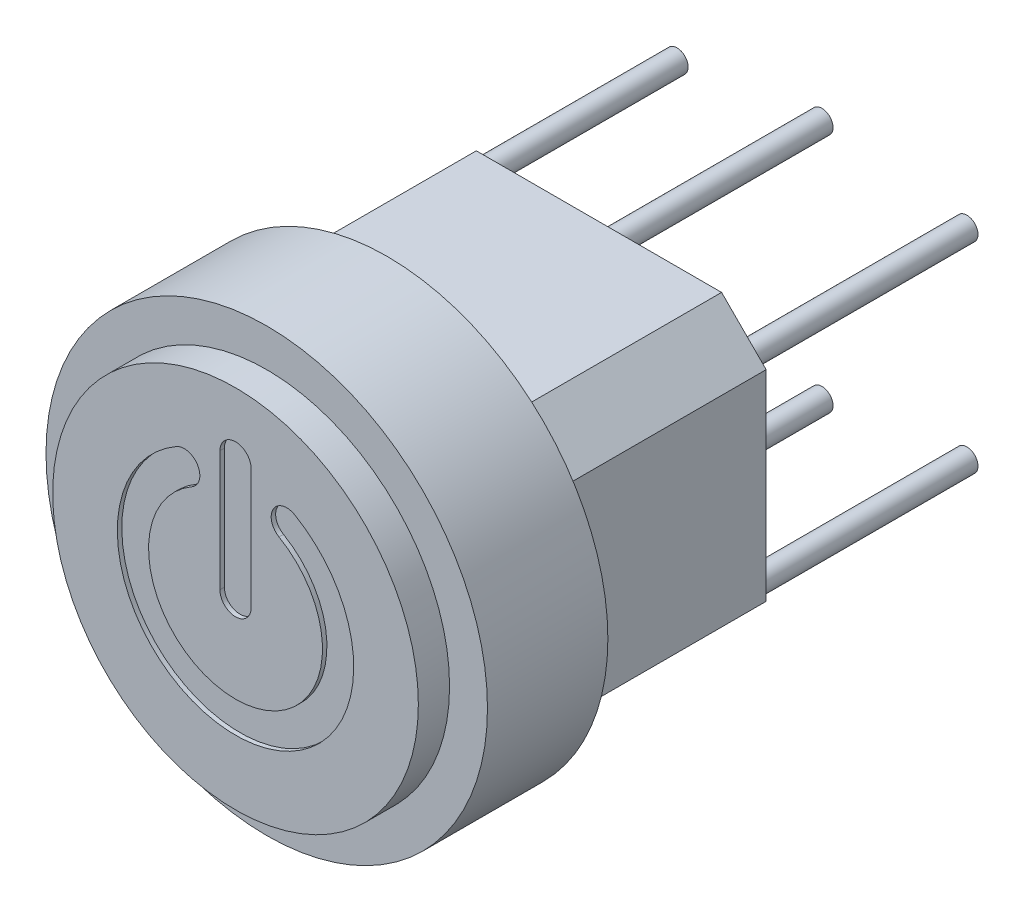
SolidWorks part; units mm, degrees
ref_plane "Plan de face" through (0, 0, 0) normal (0, 0, 1) x (1, 0, 0)
ref_plane "Plan de dessus" through (0, 0, 0) normal (0, 1, 0) x (1, 0, 0)
ref_plane "Plan de droite" through (0, 0, 0) normal (1, 0, 0) x (0, 0, -1)
sketch "Esquisse1" plane through (0, 0, 0) normal (0, 0, 1) x (1, 0, 0)
  circle A0 centre (0, 0) radius 4.95
  dimension "D1" = 9.9
extrude "Boss.-Extru.1" add sketch "Esquisse1" along normal blind 2.7
sketch "Esquisse2" plane through (0, 0, 0) normal (0, 0, -1) x (-1, 0, 0)
  line L1 (-3.75, 3.25) -> (3.75, 3.25)
  line L2 (-3.75, 3.25) -> (-3.75, -3.25)
  line L3 (-3.75, -3.25) -> (3.75, -3.25)
  line L4 (3.75, 3.25) -> (3.75, -3.25)
  line L5 (-3.75, 3.25) -> (3.75, -3.25) construction
  line L6 (-3.75, -3.25) -> (3.75, 3.25) construction
  point P0 (0, 0)
  dimension "D1" = 6.5
  dimension "D2" = 7.5
extrude "Boss.-Extru.2" add sketch "Esquisse2" along normal blind 4.75
sketch "Esquisse3" plane through (0, 0, 2.7) normal (0, 0, 1) x (1, 0, 0)
  circle A0 centre (0, 0) radius 4.1
  dimension "D1" = 8.2
extrude "Boss.-Extru.3" add sketch "Esquisse3" along normal blind 0.7
chamfer "Chanfrein1" distance 1 angle 45 4 edges at (-3.75, 3.25, -2.375) (-3.75, -3.25, -2.375) (3.75, -3.25, -2.375) (3.75, 3.25, -2.375)
sketch "Esquisse4" plane through (0, 0, -4.75) normal (0, 0, -1) x (-1, 0, 0)
  line L0 (0, -3.25) -> (0, 3.25) construction
  line L1 (-2.75, -3.25) -> (2.75, -3.25) construction
  line L2 (2.75, 3.25) -> (-2.75, 3.25) construction
  line L3 (-3.25, 2.25) -> (3.25, 2.25) construction
  line L4 (-3.75, 0) -> (3.75, 0) construction
  line L5 (-3.75, 2.25) -> (-3.75, -2.25) construction
  line L6 (3.75, -2.25) -> (3.75, 2.25) construction
  circle A0 centre (-3.25, 2.25) radius 0.25
  circle A1 centre (0, 2.7) radius 0.25
  circle A2 centre (3.25, 2.25) radius 0.25
  circle A3 centre (3.25, -2.25) radius 0.25
  circle A4 centre (0, -2.7) radius 0.25
  circle A5 centre (-3.25, -2.25) radius 0.25
  point P12 (0, 2.25)
  point P13 (0, 0)
  dimension "D2" = 0.5
  dimension "D3" = 0.5
  dimension "D4" = 0.5
  dimension "D1" = 6.5
  dimension "D5" = 2.25
  dimension "D6" = 2.7
extrude "Boss.-Extru.4" add sketch "Esquisse4" along normal blind 5
sketch "Esquisse5" plane through (0, 0, 3.4) normal (0, 0, 1) x (1, 0, 0)
  line L0 (1.325, 2.295) -> (0.975, 1.6887) construction
  line L1 (-1.325, 2.295) -> (-0.975, 1.6887) construction
  line L2 (0.975, 1.6887) -> (0, 0) construction
  line L3 (0, 0) -> (-0.975, 1.6887) construction
  line L4 (0, 0) -> (0, 2.7) construction
  line L5 (0, 2.7) -> (0, 0) construction
  line L6 (0.35, 2.7) -> (0.35, 0)
  line L7 (-0.35, 2.7) -> (-0.35, 0)
  arc A0 (-0.975, 1.6887) -> (0.975, 1.6887) centre (0, 0) ccw
  arc A1 (-1.325, 2.295) -> (1.325, 2.295) centre (0, 0) ccw
  arc A2 (-1.325, 2.295) -> (-0.975, 1.6887) centre (-1.15, 1.9919) cw
  arc A3 (1.325, 2.295) -> (0.975, 1.6887) centre (1.15, 1.9919) ccw
  arc A4 (0.35, 2.7) -> (-0.35, 2.7) centre (0, 2.7) ccw
  arc A5 (-0.35, 0) -> (0.35, 0) centre (0, 0) ccw
  point P11 (0, 1.35)
  dimension "D5" = 0.35
  dimension "D6" = 2.3
  dimension "D1" = 30
  dimension "D2" = 30
  dimension "D3" = 2.7
  dimension "D4" = 0.7
extrude "Enlèv. mat.-Extru.1" cut sketch "Esquisse5" against normal blind 0.1 contours L7 A5 L6 A4 | A1 A3 A0 A2 region at (0, 1.35, 3.4) region at (0, -2.0228, 3.4)
